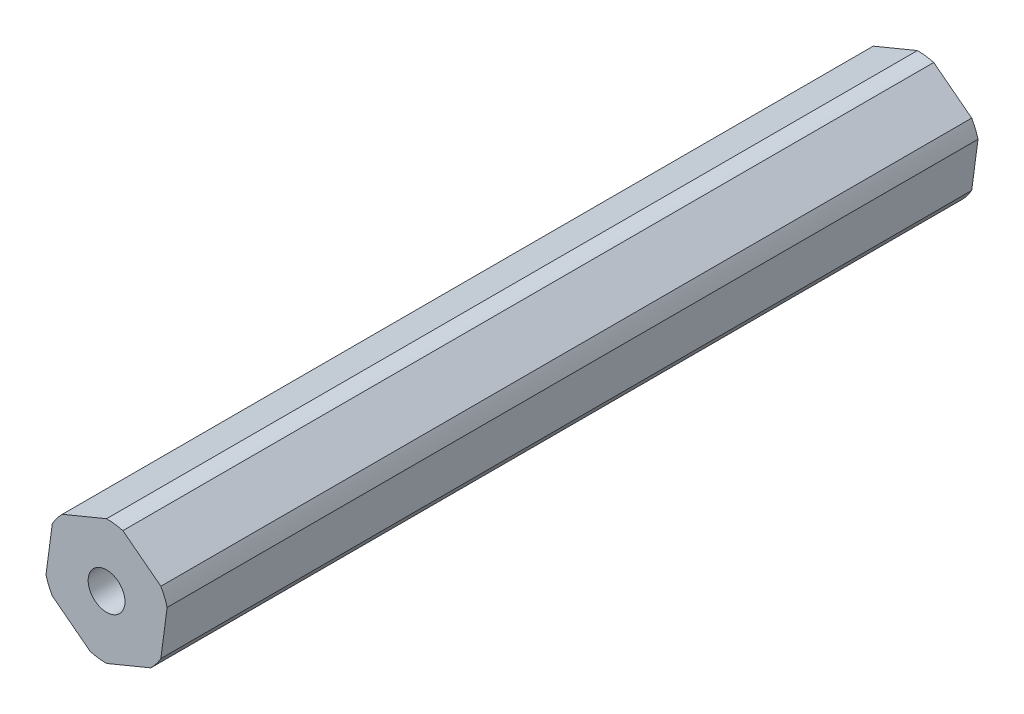
SolidWorks part; units mm, degrees
material "6061-T6 (SS)"
ref_plane "Front Plane" through (0, 0, 0) normal (0, 0, 1) x (1, 0, 0)
ref_plane "Top Plane" through (0, 0, 0) normal (0, 1, 0) x (1, 0, 0)
ref_plane "Right Plane" through (0, 0, 0) normal (1, 0, 0) x (0, 0, -1)
sketch "Sketch1" plane through (0, 0, 0) normal (0, 0, 1) x (1, 0, 0)
  line L1 (5.9502, 3.4353) -> (1.7899, 6.6335)
  line L2 (0, 6.8707) -> (-4.8498, 4.8668)
  line L3 (-5.9502, 3.4353) -> (-6.6397, -1.7666)
  line L4 (-5.9502, -3.4354) -> (-1.7899, -6.6335)
  line L5 (0, -6.8707) -> (4.8498, -4.8668)
  line L6 (5.9502, -3.4354) -> (6.6397, 1.7666)
  circle A0 centre (0, 0) radius 6.35 construction
  arc A1 (1.7899, 6.6335) -> (0, 6.8707) centre (0, 0) ccw
  arc A2 (6.6397, 1.7666) -> (5.9502, 3.4353) centre (0, 0) ccw
  arc A3 (4.8498, -4.8668) -> (5.9502, -3.4354) centre (0, 0) ccw
  arc A4 (-1.7899, -6.6335) -> (0, -6.8707) centre (0, 0) ccw
  arc A5 (-6.6397, -1.7666) -> (-5.9502, -3.4354) centre (0, 0) ccw
  arc A6 (-4.8498, 4.8668) -> (-5.9502, 3.4353) centre (0, 0) ccw
  dimension "D1" = 13.7414
  dimension ".5" = 12.7
extrude "Boss-Extrude1" add sketch "Sketch1" along normal blind 88.9
hole_wizard "#10-32 Tapped Hole1" positions "Sketch3" profile "Sketch4" tap size "#10-32" standard "ANSI Inch"
sketch "Sketch3" plane through (0, 0, 88.9) normal (0, 0, 1) x (1, 0, 0)
  point P0 (0, 0)
sketch "Sketch4" plane through (0, 0, 88.9) normal (1, 0, 0) x (0, -1, 0)
  line L0 (0, 0) -> (0, 13.2529)
  line L1 (0, 13.2529) -> (2.0193, 12.0396)
  line L2 (2.0193, 12.0396) -> (2.0193, 0)
  line L5 (2.0193, 0) -> (0, 0)
  line L10 (0, 13.2529) -> (-2.0193, 12.0396) construction
  line L11 (0, -6.35) -> (0, 107.95) construction
  dimension "Tap Drill Dia." = 4.0386
  dimension "Tap Drill Depth" = 12.0396
  dimension "Drill Angle" = 118
cosmetic thread "Hole Thread1"
hole_wizard "#10-32 Tapped Hole2" positions "Sketch6" profile "Sketch5" tap size "#10-32" standard "ANSI Inch"
sketch "Sketch6" plane through (0, 0, 0) normal (0, 0, -1) x (-1, 0, 0)
  point P0 (0, 0)
sketch "Sketch5" plane through (0, 0, 0) normal (1, 0, 0) x (0, 1, 0)
  line L0 (0, 0) -> (0, 13.2529)
  line L1 (0, 13.2529) -> (2.0193, 12.0396)
  line L2 (2.0193, 12.0396) -> (2.0193, 0)
  line L5 (2.0193, 0) -> (0, 0)
  line L10 (0, 13.2529) -> (-2.0193, 12.0396) construction
  line L11 (0, -6.35) -> (0, 107.95) construction
  dimension "Tap Drill Dia." = 4.0386
  dimension "Tap Drill Depth" = 12.0396
  dimension "Drill Angle" = 118
cosmetic thread "Hole Thread2" parameters "D1"=9.652, "D2"=4.826
